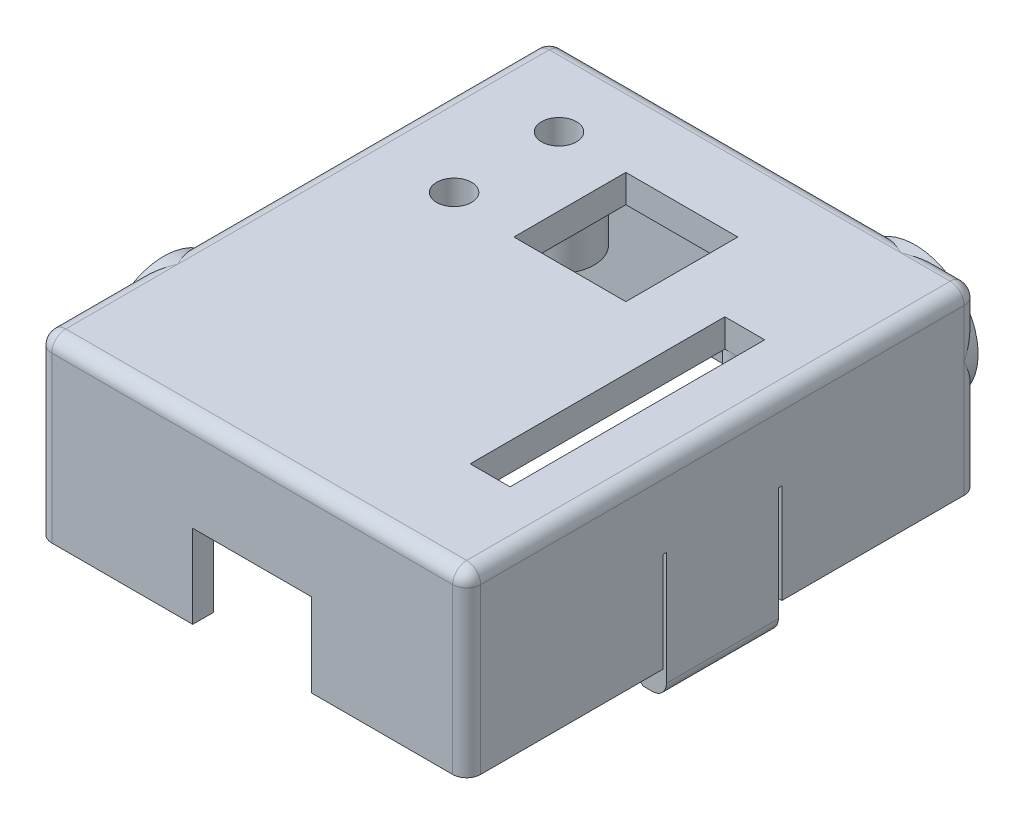
SolidWorks part; units mm, degrees
other "Markup1"
sketch "Sketch4" plane through (13.425, 5.65, 17.4168) normal (0.3982, 0.1503, 0.9049) x (0.9155, -0.0036, -0.4023)
sketch "Sketch28" plane through (15.325, 10.45, 18.275) normal (0.3982, 0.1503, 0.9049) x (0.9155, -0.0036, -0.4023)
ref_plane "Front Plane" through (0, 0, 0) normal (0, 0, 1) x (1, 0, 0)
ref_plane "Top Plane" through (0, 0, 0) normal (0, 1, 0) x (1, 0, 0)
ref_plane "Right Plane" through (0, 0, 0) normal (1, 0, 0) x (0, 0, -1)
sketch "Sketch1" plane through (0, -2.3, 0) normal (0, 1, 0) x (1, 0, 0)
  line L0 (-15.325, 4.25) -> (-13.35, 4.25)
  line L1 (-15.325, 4.25) -> (-15.325, 17.275) construction
  line L2 (-13.35, 4.25) -> (-13.35, 16.8)
  line L3 (-13.35, 16.8) -> (13.35, 16.8)
  line L4 (13.35, 16.8) -> (13.35, 4.25)
  line L5 (13.35, 4.25) -> (15.325, 4.25)
  line L6 (15.325, 17.275) -> (15.325, 4.25) construction
  line L7 (15.325, 4.25) -> (15.325, 18.275)
  line L8 (15.325, 18.275) -> (-15.325, 18.275)
  line L9 (-15.325, 18.275) -> (-15.325, 4.25)
  line L10 (-13.35, 16.8) -> (-13.35, 18.275) construction
  line L11 (-13.3, -4.5551) -> (-13.3, 16.75) construction
  line L12 (-13.3, 16.75) -> (6.1051, 16.75) construction
  line L13 (11.825, -4.25) -> (13.3, -4.25) construction
  line L14 (0, 0) -> (6.485, 0) construction
  line L16 (15.325, -18.275) -> (4.25, -18.275)
  line L17 (15.325, -4.25) -> (15.325, -18.275)
  line L18 (13.35, -4.25) -> (15.325, -4.25)
  line L19 (13.35, -16.8) -> (13.35, -4.25)
  line L24 (4.25, -16.8) -> (4.25, -18.275)
  line L25 (4.25, -17.5375) -> (-4.25, -17.5375) construction
  line L26 (0, -17.5375) -> (0, -18.275) construction
  line L28 (4.25, -16.8) -> (13.35, -16.8)
  line L29 (-4.2, -18.275) -> (4.2, -18.275) construction
  line L30 (15.325, -4.25) -> (15.325, -17.275) construction
  line L31 (-13.3, 4.25) -> (-15.325, 4.25) construction
  line L32 (-13.35, -4.25) -> (-15.325, -4.25)
  line L33 (-15.325, -4.25) -> (-15.325, -18.275)
  line L34 (-13.35, -16.8) -> (-13.35, -4.25)
  line L35 (-4.25, -16.8) -> (-13.35, -16.8)
  line L36 (-4.25, -16.8) -> (-4.25, -18.275)
  line L37 (-15.325, -18.275) -> (-4.25, -18.275)
  line L38 (-14.325, 18.275) -> (14.325, 18.275) construction
  dimension "D2" = 0.05
  dimension "D3" = 0.05
  dimension "D4" = 8.5
  dimension "D1" = 0
extrude "bottom" add sketch "Sketch1" along normal up to surface (6.6 mm away)
sketch "Sketch2" plane through (0, 0.8, 0) normal (0, 1, 0) x (1, 0, 0)
  line L16 (13.35, 4.25) -> (13.35, 16.8) construction
  line L17 (4.25, -18.275) -> (4.25, -16.8) construction
  line L18 (-15.325, 18.275) -> (15.325, 18.275)
  line L19 (-15.325, 18.275) -> (-15.325, -18.275)
  line L20 (15.325, 18.275) -> (15.325, -18.275)
  line L21 (-15.325, -18.275) -> (-4.25, -18.275)
  line L22 (-13.35, 16.8) -> (13.35, 16.8)
  line L23 (-13.35, 16.8) -> (-13.35, -16.8)
  line L24 (13.35, 16.8) -> (13.35, -16.8)
  line L25 (-13.35, -16.8) -> (-4.25, -16.8)
  line L28 (-4.25, -16.8) -> (-4.25, -18.275)
  line L29 (4.25, -16.8) -> (4.25, -18.275)
  line L30 (4.25, -16.8) -> (13.35, -16.8)
  line L31 (4.25, -18.275) -> (15.325, -18.275)
  line L32 (4.25, -18.275) -> (15.325, -18.275) construction
  line L33 (13.35, -16.8) -> (4.25, -16.8) construction
  line L34 (-14.325, 18.275) -> (14.325, 18.275) construction
  line L35 (15.325, 17.275) -> (15.325, 4.25) construction
  line L36 (-15.325, 4.25) -> (-15.325, 18.275) construction
  circle A0 centre (-8.9, 8.55) radius 1.5
  circle A1 centre (8.9, 8.55) radius 1.5
  circle A2 centre (8.9, -13.05) radius 1.5
  circle A3 centre (-8.9, -13.05) radius 1.5
  circle A4 centre (-8.9, -13.05) radius 1.5 construction
  circle A5 centre (-8.9, 8.55) radius 1.5 construction
  circle A6 centre (8.9, 8.55) radius 1.5 construction
  circle A7 centre (8.9, -13.05) radius 1.5 construction
extrude "sides" add sketch "Sketch2" along normal offset from surface (7.65 mm away) 0.25 offset beyond the face yes
sketch "Sketch3" plane through (0, 8.45, 0) normal (0, 1, 0) x (1, 0, 0)
  line L4 (-6.35, 14.775) -> (6.35, 2.075) construction
  line L9 (-15.325, -18.275) -> (-4.25, -18.275) construction
  line L10 (-15.325, 18.275) -> (15.325, 18.275)
  line L11 (-15.325, 18.275) -> (-15.325, -18.275)
  line L12 (15.325, 18.275) -> (15.325, -18.275)
  line L13 (-15.325, -18.275) -> (15.325, -18.275)
  line L15 (-4, 12.425) -> (4, 12.425)
  line L16 (-4, 12.425) -> (-4, 4.425)
  line L17 (-4, 4.425) -> (4, 4.425)
  line L18 (4, 12.425) -> (4, 4.425)
  line L19 (-4, 12.425) -> (4, 4.425) construction
  line L20 (-4, 4.425) -> (4, 12.425) construction
  point P6 (0, 8.425)
  dimension "D1" = 8
extrude "top" add sketch "Sketch3" along normal blind 2
combine bodies "Combine1" operation type add bodies to combine 111 104 138 137 136 135 125 114 103
sketch "Sketch5" plane through (0, 0, 0) normal (0, 0, 1) x (1, 0, 0)
  line L0 (-15.325, 0.8) -> (-15.325, -4.3)
  line L2 (-12.45, -2.2) -> (-13.35, -2.3)
  line L3 (-13.35, 0.8) -> (-13.35, -2.3)
  line L4 (-15.325, 0.8) -> (-13.35, 0.8)
  line L5 (-12.45, -2.2) -> (-12.45, -3.1)
  line L7 (-15.325, -4.3) -> (-13.65, -4.3)
  line L8 (-13.65, -4.3) -> (-12.45, -3.1)
  line L10 (-13.35, 0.8) -> (-13.35, -2.3) construction
  line L11 (-15.325, 10.45) -> (-15.325, -2.3) construction
  line L12 (-15.325, 0.8) -> (-13.35, 0.8) construction
  line L13 (14.325, -4.3) -> (-14.325, -4.3) construction
  line L14 (-15.325, -2.3) -> (-4.25, -2.3) construction
  dimension "D1" = 0.9
  dimension "D2" = 0.1
  dimension "D3" = 1.2
  dimension "D4" = 1.2
extrude "tab extrude" add sketch "Sketch5" along normal mid plane 8
mirror "tab mirror" about plane through (0, 0, 0) normal (1, 0, 0) of "tab extrude"
sketch "Sketch6" plane through (0, 0, 18.275) normal (0, 0, 1) x (1, 0, 0)
  line L1 (-4.25, 8.45) -> (4.25, 8.45)
  line L2 (-4.25, 8.45) -> (-4.25, 3.65)
  line L3 (-4.25, 3.65) -> (4.25, 3.65)
  line L4 (4.25, 8.45) -> (4.25, 3.65)
  line L5 (-4, 3.4) -> (4, 3.4) construction
  line L6 (4.25, 8.45) -> (4.25, -2.3) construction
  dimension "D1" = 0.25
extrude "port top" add sketch "Sketch6" against normal up to surface (1.475 mm away) up to face at (-8.8, 3.075, 16.8)
sketch "Sketch18" plane through (0, 8.45, 0) normal (0, -1, 0) x (-1, 0, 0)
  circle A1 centre (8.9, 5.05) radius 1.25
  circle A3 centre (8.9, 12.55) radius 1.25
  point P0 (8.9, 8.55)
  dimension "D2" = 2.5
  dimension "D4" = 0
  dimension "D1" = 4
  dimension "D3" = 0
  dimension "D5" = 3.5
extrude "button cut" cut sketch "Sketch18" against normal blind 10
sketch "Sketch25" plane through (0, 8.45, 0) normal (0, -1, 0) x (1, 0, 0)
  circle A0 centre (-8.9, -5.05) radius 1.75
  circle A1 centre (-8.9, -12.55) radius 1.75
  circle A2 centre (-8.9, -5.05) radius 2.505
  circle A3 centre (-8.9, -12.55) radius 2.505
  dimension "D1" = 3.5
  dimension "D2" = 5.01
extrude "button holders" add sketch "Sketch25" along normal blind 5
fillet "Fillet1" radius 1 10 edges at (15.325, 10.45, 0) (0, 10.45, 18.275) (-15.325, 4.075, 18.275) (0, 10.45, -18.275) (-15.325, 10.45, 0) (15.325, -4.3, 0) (-15.325, -4.3, 0) (-15.325, 4.075, -18.275) (15.325, 4.075, -18.275) (15.325, 4.075, 18.275)
sketch "Sketch19" plane through (0, 0, -18.275) normal (0, 0, -1) x (-1, 0, 0)
  line L1 (-15.325, 0.8) -> (-15.325, -3.3) construction
  line L3 (14.325, 10.45) -> (-14.325, 10.45) construction
  circle A0 centre (-10.825, 5.95) radius 4.5
  dimension "D1" = 9
extrude "Boss-Extrude8" add sketch "Sketch19" against normal blind 8
sketch "Sketch20" plane through (0, 0, -18.275) normal (0, 0, -1) x (-1, 0, 0)
  circle A0 centre (-10.825, 5.95) radius 2.3749
  dimension "D1" = 4.7498
extrude "Cut-Extrude4" cut sketch "Sketch20" against normal blind 6
sketch "Sketch23" plane through (0, 0, -10.275) normal (0, 0, 1) x (1, 0, 0)
  circle A0 centre (10.825, 5.95) radius 4.5
  circle A1 centre (10.825, 5.95) radius 4.5 construction
extrude "Boss-Extrude9" add sketch "Sketch23" against normal blind 2
thread "Thread3" pitch 1.27 method cut profile "Thread Profile3" start angle 0, offset 1, length 0, pitch 1.27, diameter 4.7498
ref_plane "Plane3" through (13.1999, 5.95, -19.275) normal (0, -1, 0) x (1, 0, 0)
sketch "Thread Profile3" plane through (13.1999, 5.95, -19.275) normal (0, -1, 0) x (1, 0, 0)
  line L0 (0, 0) -> (0, 1.27) construction
  line L1 (0, 0) -> (0.6874, 0.3969)
  line L2 (0.6874, 0.3969) -> (0.6874, 0.5556)
  line L3 (0.6874, 0.5556) -> (0, 0.9525)
  line L4 (0.6874, 0.4762) -> (0, 0.4762) construction
  line L11 (0, 0) -> (0, 0.9525)
  point P2 (0, 0)
  dimension "Pitch" = 1.27
  dimension "Profile_Angle" = 60
  dimension "Profile_Land" = 0.1588
  dimension "Profile_Height" = 0.6874
sketch "Sketch7" plane through (-15.325, -4.875, 0) normal (1, 0, 0) x (0, -1, 0)
  line L1 (-14.325, -18.275) -> (-2.575, -18.275) construction
  line L2 (-15.325, 17.275) -> (-15.325, -17.275) construction
  circle A0 centre (-10.825, -9.275) radius 4.5
  dimension "D2" = 9
  dimension "D1" = 9
extrude "Boss-Extrude6" add sketch "Sketch7" along normal blind 8
sketch "Sketch8" plane through (-15.325, -4.875, 0) normal (1, 0, 0) x (0, -1, 0)
  circle A0 centre (-10.825, -9.275) radius 2.3749
  dimension "D1" = 4.7498
extrude "Cut-Extrude1" cut sketch "Sketch8" along normal blind 6
thread "Thread1" pitch 1.27 method cut profile "Thread Profile1" start angle 0, offset 1, length 0, pitch 1.27, diameter 4.7498
ref_plane "Plane1" through (-16.325, 5.95, 6.9001) normal (0, -1, 0) x (0, 0, -1)
sketch "Thread Profile1" plane through (-16.325, 5.95, 6.9001) normal (0, -1, 0) x (0, 0, -1)
  line L0 (0, 0) -> (0, 1.27) construction
  line L1 (0, 0) -> (0.6874, 0.3969)
  line L2 (0.6874, 0.3969) -> (0.6874, 0.5556)
  line L3 (0.6874, 0.5556) -> (0, 0.9525)
  line L4 (0.6874, 0.4762) -> (0, 0.4762) construction
  line L11 (0, 0) -> (0, 0.9525)
  point P2 (0, 0)
  dimension "Pitch" = 1.27
  dimension "Profile_Angle" = 60
  dimension "Profile_Land" = 0.1588
  dimension "Profile_Height" = 0.6874
mirror "Mirror4" [suppressed] about plane through (0, 0, 0) normal (1, 0, 0)
thread "Thread4" [suppressed] pitch 1.27 start angle 0, offset 1, length 0, pitch 1.27, diameter 4.7498
ref_plane "Plane4" through (16.325, 6.45, 11.6499) normal (0, -1, 0) x (0, 0, 1)
sketch "Thread Profile4" plane through (16.325, 6.45, 11.6499) normal (0, -1, 0) x (0, 0, 1)
  line L0 (0, 0) -> (0, 1.27) construction
  line L1 (0, 0) -> (0.6874, 0.3969)
  line L2 (0.6874, 0.3969) -> (0.6874, 0.5556)
  line L3 (0.6874, 0.5556) -> (0, 0.9525)
  line L4 (0.6874, 0.4762) -> (0, 0.4762) construction
  line L11 (0, 0) -> (0, 0.9525)
  point P2 (0, 0)
  dimension "Pitch" = 1.27
  dimension "Profile_Angle" = 60
  dimension "Profile_Land" = 0.1588
  dimension "Profile_Height" = 0.6874
sketch "Sketch17" plane through (-7.325, 0, 0) normal (1, 0, 0) x (0, 0, -1)
  circle A0 centre (-9.275, 5.95) radius 4.5
  arc A1 (-13.0167, 8.45) -> (-5.5333, 8.45) centre (-9.275, 5.95) ccw construction
extrude "Boss-Extrude7" add sketch "Sketch17" against normal blind 2
mirror "Mirror5" [suppressed] about plane through (0, 0, 0) normal (1, 0, 0)
sketch "Sketch24" plane through (0, 8.45, 0) normal (0, -1, 0) x (1, 0, 0)
  line L0 (8.525, 11.125) -> (11.275, -6.975) construction
  line L1 (8.475, 11.175) -> (11.325, 11.175)
  line L2 (8.475, 11.175) -> (8.475, -7.025)
  line L3 (8.475, -7.025) -> (11.325, -7.025)
  line L4 (11.325, 11.175) -> (11.325, -7.025)
  line L5 (8.475, 11.175) -> (11.325, -7.025) construction
  line L6 (8.475, -7.025) -> (11.325, 11.175) construction
  line L7 (8.525, 11.125) -> (8.525, 11.175) construction
  line L8 (8.525, 11.125) -> (8.475, 11.125) construction
  point P0 (9.9, 2.075)
  dimension "D1" = 0.05
extrude "head cut" cut sketch "Sketch24" against normal through all
sketch "Sketch26" plane through (0, 0.8, 0) normal (0, -1, 0) x (1, 0, 0)
  circle A0 centre (-8.9, -8.55) radius 1
  circle A1 centre (-8.9, 13.05) radius 1
  circle A2 centre (8.9, 13.05) radius 1
  circle A3 centre (8.9, -8.55) radius 1
  dimension "D1" = 2
extrude "Boss-Extrude10" add sketch "Sketch26" along normal blind 1.6
sketch "Sketch27" plane through (-15.325, 0, 0) normal (-1, 0, 0) x (0, 0, 1)
  line L0 (-4.25, 0.8) -> (-4, 0.8)
  line L1 (-4.25, 0.8) -> (-4.25, 4.8)
  line L2 (-4, 0.8) -> (-4, 4.8)
  line L3 (-4.25, 4.8) -> (-4, 4.8)
  line L4 (4, 0.8) -> (4.25, 0.8)
  line L5 (4, 0.8) -> (4, 4.8)
  line L6 (4.25, 0.8) -> (4.25, 4.8)
  line L7 (4, 4.8) -> (4.25, 4.8)
  dimension "D1" = 4
extrude "Cut-Extrude5" cut sketch "Sketch27" against normal through all
equation "\"D3@Sketch1\"=\"D2@Sketch1\""
equation "\"D1@Sketch8\"=.187in"
equation "\"D1@Sketch20\"=.187in"
